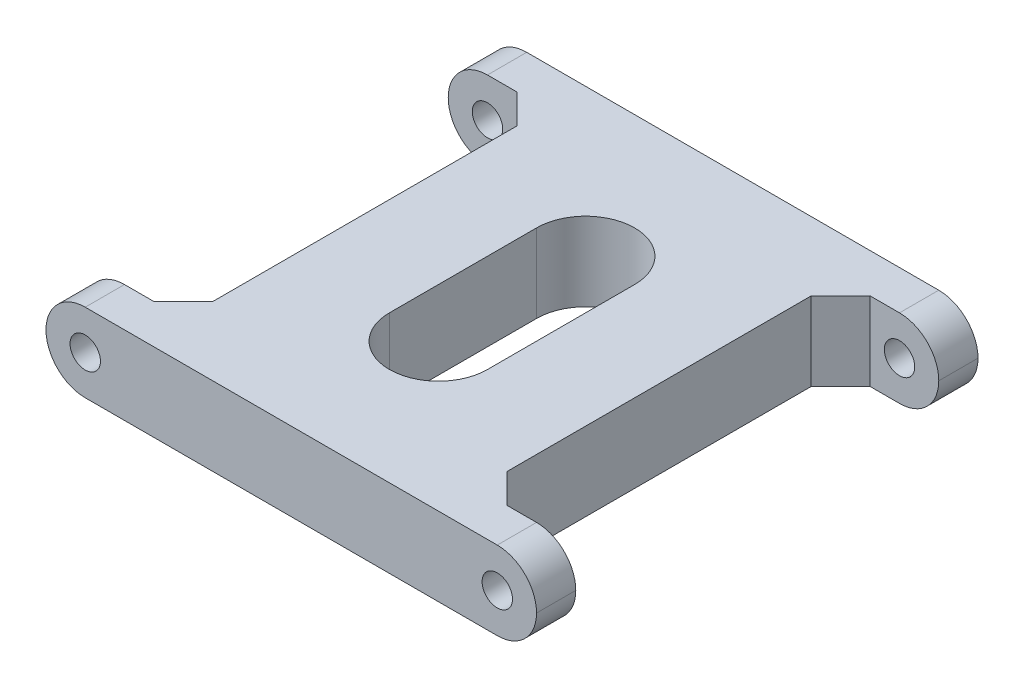
SolidWorks part; units mm, degrees
material "6061 Alloy"
ref_plane "前视基准面" through (0, 0, 0) normal (0, 0, 1) x (1, 0, 0)
ref_plane "上视基准面" through (0, 0, 0) normal (0, 1, 0) x (1, 0, 0)
ref_plane "右视基准面" through (0, 0, 0) normal (1, 0, 0) x (0, 0, -1)
sketch "Sketch1" plane through (0, 0, 0) normal (0, 1, 0) x (1, 0, 0)
  line L0 (0, 0) -> (0, 26.9649) construction
  line L1 (0, 0) -> (41.2475, 0) construction
  line L2 (-25, 22.5) -> (25, 22.5)
  line L3 (25, 22.5) -> (25, 18.5)
  line L4 (25, 18.5) -> (15, 18.5)
  line L5 (15, 18.5) -> (15, -18.5)
  line L6 (-15, 18.5) -> (-15, -18.5)
  line L7 (-25, 18.5) -> (-15, 18.5)
  line L8 (-25, 22.5) -> (-25, 18.5)
  line L9 (-25, -22.5) -> (-25, -18.5)
  line L10 (-25, -18.5) -> (-15, -18.5)
  line L11 (25, -18.5) -> (15, -18.5)
  line L12 (25, -22.5) -> (25, -18.5)
  line L13 (-25, -22.5) -> (25, -22.5)
  line L14 (0, -7.5) -> (0, 7.5) construction
  line L15 (-5, -7.5) -> (-5, 7.5)
  line L16 (5, -7.5) -> (5, 7.5)
  arc A0 (-5, -7.5) -> (5, -7.5) centre (0, -7.5) ccw
  arc A1 (5, 7.5) -> (-5, 7.5) centre (0, 7.5) ccw
  point P13 (0, 22.5)
  point P16 (-15, 0)
  point P17 (15, 0)
  point P21 (0, 0)
  dimension "D6" = 5
  dimension "D1" = 25
  dimension "D2" = 4
  dimension "D3" = 10
  dimension "D4" = 45
  dimension "D5" = 15
extrude "Boss-Extrude1" add sketch "Sketch1" along normal mid plane 8
chamfer "Chamfer1" distance 3 angle 45 4 edges at (15, 0, 18.5) (-15, 0, 18.5) (-15, 0, -18.5) (15, 0, -18.5)
sketch "Sketch3" plane through (0, 0, 0) normal (0, 0, 1) x (1, 0, 0)
  line L0 (0, 0) -> (-42.1534, 0) construction
  line L1 (-25, 4) -> (-25, -4) construction
  line L2 (0, 0) -> (0, -12.8718) construction
  circle A0 centre (-21, 0) radius 1.55
  circle A1 centre (21, 0) radius 1.55
  dimension "D1" = 4
  dimension "D2" = 3.1
extrude "Cut-Extrude1" cut sketch "Sketch3" against normal through all both and the other way through all
fillet "Fillet1" radius 4 8 edges at (25, -4, 20.5) (-25, -4, 20.5) (-25, 4, 20.5) (25, 4, 20.5) (25, -4, -20.5) (25, 4, -20.5) (-25, -4, -20.5) (-25, 4, -20.5)
